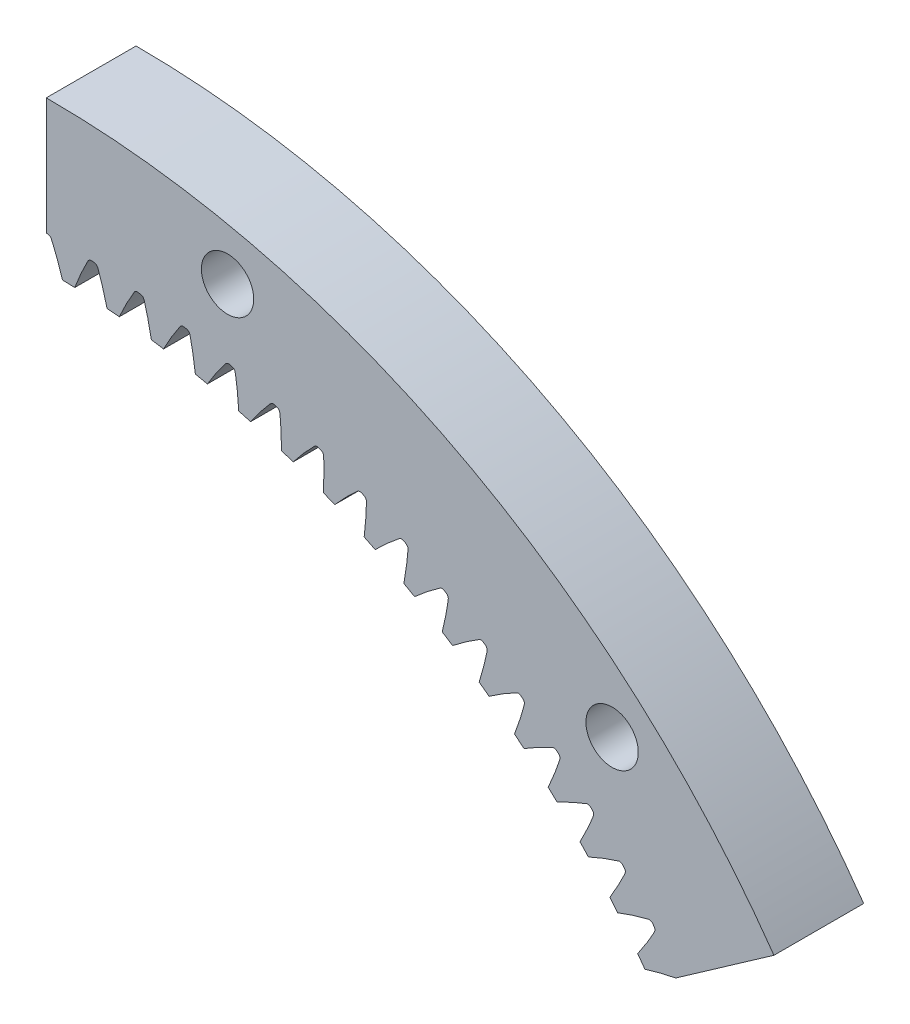
SolidWorks part; units mm, degrees
material "Д16 ГОСТ 4784-97"
ref_plane "FRONT" through (0, 0, 0) normal (0, 0, 1) x (1, 0, 0)
ref_plane "TOP" through (0, 0, 0) normal (0, 1, 0) x (1, 0, 0)
ref_plane "RIGHT" through (0, 0, 0) normal (1, 0, 0) x (0, 0, -1)
ref_axis "Ось1" through (0, 0, 50) along (0, 0, -1)
sketch "SketchRevolveSpurAssemblyNew2Gear" plane through (0, 0, 0) normal (1, 0, 0) x (0, 0, -1)
  line L0 (0, 0) -> (1, 0) construction
  line L1 (-2, 49.399) -> (-2, 59.399)
  line L2 (-2, 59.399) -> (4, 59.399)
  line L3 (4, 59.399) -> (4, 49.399)
  line L4 (4, 49.399) -> (-2, 49.399)
  dimension "MinorDiameter" = 49.399
  dimension "D1" = 6
  dimension "D2" = 10
revolve "SpurAssemblyNew2Gear" add sketch "SketchRevolveSpurAssemblyNew2Gear" angle 360 about L0
sketch "SketchToothSpurAssemblyNew2Gear" plane through (0, 0, 0) normal (0, 0, 1) x (1, 0, 0)
  arc A0 (49.1395, -1.1537) -> (49.1395, 1.1537) centre (0, 0) ccw
  spline S0 degree 3 poles (49.1395, 1.1537) (49.2861, 1.1124) (49.5102, 1.0454) (49.8138, 0.9473) (50.0554, 0.8652) (50.306, 0.7758) (50.5651, 0.6788) (50.8329, 0.5746) (51.108, 0.4599) (51.3094, 0.3804) (51.4272, 0.3224) (51.4611, 0.2973) (51.4911, 0.268) (51.5164, 0.2347) (51.5367, 0.198) (51.5565, 0.1461) (51.5633, 0.0916) (51.5623, 0.0385) (51.5626, 0) (51.5623, -0.0385) (51.5633, -0.0916) (51.5565, -0.1461) (51.5367, -0.198) (51.5164, -0.2347) (51.4911, -0.268) (51.4611, -0.2973) (51.4272, -0.3224) (51.3094, -0.3804) (51.108, -0.4599) (50.8329, -0.5746) (50.5651, -0.6788) (50.306, -0.7758) (50.0554, -0.8652) (49.8138, -0.9473) (49.5102, -1.0454) (49.2861, -1.1124) (49.1395, -1.1537) knots 0 0 0 0 0.081489 0.125094 0.170606 0.218025 0.26735 0.318583 0.371722 0.426768 0.434365 0.441808 0.449251 0.456695 0.464138 0.471581 0.486277 0.493139 0.5 0.506861 0.513723 0.528419 0.535862 0.543305 0.550749 0.558192 0.565635 0.573232 0.628278 0.681417 0.73265 0.781975 0.829394 0.874906 0.918511 1 1 1 1
extrude "ToothExtrudeCutSpurAssemblyNew2Gear" cut sketch "SketchToothSpurAssemblyNew2Gear" against normal blind 4 and the other way blind 4
pattern_circular "PatternSpurAssemblyNew2Gear" count 104 every 3.462 about axis through (0, 0, 50) along (0, 0, -1) of "ToothExtrudeCutSpurAssemblyNew2Gear"
sketch "AuxiliarySketchSpurAssemblyNew2Gear" plane through (0, 0, 0) normal (0, 0, 1) x (1, 0, 0)
  circle A0 centre (0, 0) radius 50 construction
  circle A1 centre (0, 0) radius 46.9846 construction
  circle A2 centre (0, 0) radius 51.5625 construction
  circle A3 centre (0, 0) radius 49.399 construction
  dimension "PitchDiameter" = 100
  dimension "BaseDiameter" = 93.9693
  dimension "MajorDiameter" = 103.125
  dimension "MinorDiameter" = 98.7981
sketch "Эскиз1" plane through (0, 0, 2) normal (0, 0, 1) x (1, 0, 0)
  line L0 (0, 0) -> (0, 59.399)
  line L1 (0, 0) -> (48.6568, 34.0699)
  line L2 (0, 0) -> (37.8331, 41.2875) construction
  line L3 (0, 0) -> (12.1206, 54.6726) construction
  line L4 (0, 0) -> (25.8579, 49.6726) construction
  arc A0 (0, 59.399) -> (48.6568, 34.0699) centre (0, 0) ccw
  arc A1 (45.8725, 32.1203) -> (0, 56) centre (0, 0) ccw construction
  circle A2 centre (12.1206, 54.6726) radius 1.75
  arc A3 (20.7548, 14.5327) -> (0, 25.337) centre (0, 0) ccw construction
  circle A4 centre (37.8331, 41.2875) radius 1.75
  circle A5 centre (0, 0) radius 59.399 construction
  point P8 (9.4258, 55.201)
  dimension "D2" = 30
  dimension "D3" = 25.337
  dimension "D4" = 3.5
  dimension "D6" = 15
  dimension "D5" = 56
  dimension "D1" = 55
extrude "Вырез-Вытянуть1" cut sketch "Эскиз1" against normal through all
